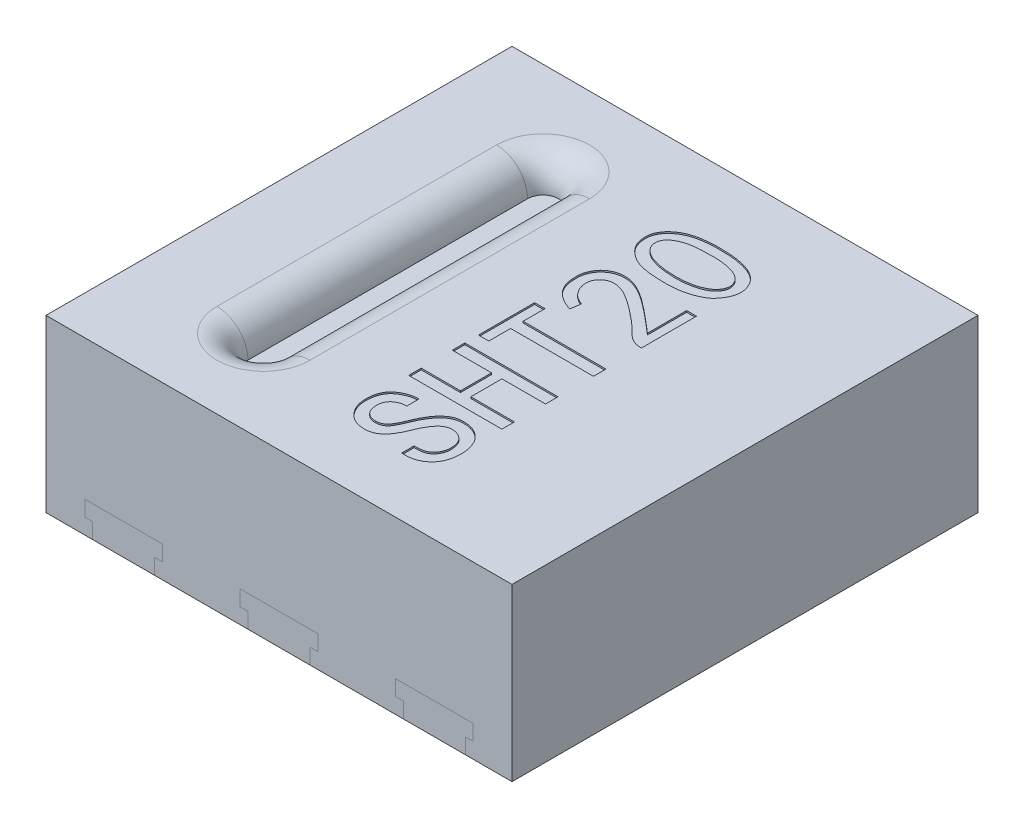
SolidWorks part; units mm, degrees
ref_plane "前视基准面" through (0, 0, 0) normal (0, 0, 1) x (1, 0, 0)
ref_plane "上视基准面" through (0, 0, 0) normal (0, 1, 0) x (1, 0, 0)
ref_plane "右视基准面" through (0, 0, 0) normal (1, 0, 0) x (0, 0, -1)
sketch "草图1" plane through (0, 0, 0) normal (0, 1, 0) x (1, 0, 0)
  line L1 (0, 0) -> (3, 0)
  line L2 (0, 0) -> (0, 3)
  line L3 (0, 3) -> (3, 3)
  line L4 (3, 0) -> (3, 3)
  dimension "D1" = 3
  dimension "D2" = 3
extrude "凸台-拉伸1" add sketch "草图1" along normal blind 1.1
sketch "草图2" plane through (0, 0, 0) normal (0, -1, 0) x (1, 0, 0)
  line L0 (-0.1538, -1.5) -> (3.2278, -1.5) construction
  line L1 (1.5, 0.1616) -> (1.5, -3.1506) construction
  line L2 (0, 0) -> (3, 0) construction
  line L3 (3, -3) -> (0, -3) construction
  line L4 (0, -3) -> (0, 0) construction
  line L5 (3, 0) -> (3, -3) construction
  line L6 (2.6, -2.25) -> (2.7, -2.15)
  line L7 (0.3, 0) -> (0.3, -0.35)
  line L8 (0.3, -0.35) -> (0.35, -0.4)
  line L9 (0.35, -0.4) -> (0.65, -0.4)
  line L10 (0.65, -0.4) -> (0.7, -0.35)
  line L11 (0.4, -0.75) -> (2.6, -0.75)
  line L12 (0.3, -0.85) -> (0.3, -2.15)
  line L13 (0.4, -2.25) -> (2.6, -2.25)
  line L14 (2.7, -0.85) -> (2.7, -2.15)
  line L15 (0.7, -0.35) -> (0.7, 0)
  line L16 (0.3, 0) -> (0.7, 0)
  line L17 (0.4, 0.0671) -> (0.4, -0.4631) construction
  line L18 (1.4, 0.0671) -> (1.4, -0.4631) construction
  line L19 (1.3, 0) -> (1.7, 0)
  line L20 (1.3, 0) -> (1.3, -0.35)
  line L21 (1.7, -0.35) -> (1.7, 0)
  line L22 (1.65, -0.4) -> (1.7, -0.35)
  line L23 (1.35, -0.4) -> (1.65, -0.4)
  line L24 (1.3, -0.35) -> (1.35, -0.4)
  line L25 (2.4, 0.0671) -> (2.4, -0.4631) construction
  line L26 (2.3, 0) -> (2.7, 0)
  line L27 (2.3, 0) -> (2.3, -0.35)
  line L28 (2.7, -0.35) -> (2.7, 0)
  line L29 (2.65, -0.4) -> (2.7, -0.35)
  line L30 (2.35, -0.4) -> (2.65, -0.4)
  line L31 (2.3, -0.35) -> (2.35, -0.4)
  line L32 (2.3, -2.65) -> (2.35, -2.6)
  line L33 (2.35, -2.6) -> (2.65, -2.6)
  line L34 (2.65, -2.6) -> (2.7, -2.65)
  line L35 (1.3, -2.65) -> (1.35, -2.6)
  line L36 (1.35, -2.6) -> (1.65, -2.6)
  line L37 (1.65, -2.6) -> (1.7, -2.65)
  line L38 (0.65, -2.6) -> (0.7, -2.65)
  line L39 (0.35, -2.6) -> (0.65, -2.6)
  line L40 (0.3, -2.65) -> (0.35, -2.6)
  line L41 (0.4, -3.0671) -> (0.4, -2.5369) construction
  line L42 (0.7, -2.65) -> (0.7, -3)
  line L43 (0.3, -3) -> (0.3, -2.65)
  line L44 (2.4, -3.0671) -> (2.4, -2.5369) construction
  line L45 (2.7, -2.65) -> (2.7, -3)
  line L46 (2.3, -3) -> (2.3, -2.65)
  line L47 (1.4, -3.0671) -> (1.4, -2.5369) construction
  line L48 (1.7, -2.65) -> (1.7, -3)
  line L49 (1.3, -3) -> (1.3, -2.65)
  line L50 (0.3, -3) -> (0.7, -3)
  line L51 (1.3, -3) -> (1.7, -3)
  line L52 (2.3, -3) -> (2.7, -3)
  arc A0 (0.3, -2.15) -> (0.4, -2.25) centre (0.4, -2.15) ccw
  arc A2 (2.7, -0.85) -> (2.6, -0.75) centre (2.6, -0.85) ccw
  arc A3 (0.3, -0.85) -> (0.4, -0.75) centre (0.4, -0.85) cw
  dimension "D5" = 0.2
  dimension "D1" = 2.4
  dimension "D2" = 1.5
  dimension "D3" = 0.1
  dimension "D4" = 0.1
  dimension "D6" = 0.3
  dimension "D7" = 0.4
  dimension "D8" = 0.4
  dimension "D9" = 135
  dimension "D10" = 135
  dimension "D11" = 0.05
  dimension "D13" = 2
  dimension "D12" = 3
sketch "草图3" plane through (0, 0, 0) normal (0, 0, 1) x (1, 0, 0)
  line L0 (0.3, 0) -> (0.3, 0.1)
  line L1 (0.3, 0) -> (0.7, 0) construction
  line L2 (-0.1538, 0) -> (3.2278, 0) construction
  line L3 (0.3, 0.1) -> (0.25, 0.1)
  line L4 (0.25, 0.1) -> (0.25, 0.2)
  line L5 (0.25, 0.2) -> (0.75, 0.2)
  line L6 (0.75, 0.2) -> (0.75, 0.1)
  line L7 (0.75, 0.1) -> (0.7, 0.1)
  line L8 (0.7, 0.1) -> (0.7, 0)
  line L9 (0, 0) -> (3, 0) construction
  line L10 (0, 1.1) -> (0, 0) construction
  line L11 (0.3, 0) -> (0.7, 0)
  line L12 (1.3, 0) -> (1.3, 0.1)
  line L13 (1.3, 0.1) -> (1.25, 0.1)
  line L14 (1.25, 0.1) -> (1.25, 0.2)
  line L15 (1.25, 0.2) -> (1.75, 0.2)
  line L16 (1.75, 0.2) -> (1.75, 0.1)
  line L17 (1.75, 0.1) -> (1.7, 0.1)
  line L18 (1.7, 0.1) -> (1.7, 0)
  line L19 (1.3, 0) -> (1.7, 0)
  line L20 (2.3, 0) -> (2.3, 0.1)
  line L21 (2.3, 0.1) -> (2.25, 0.1)
  line L22 (2.25, 0.1) -> (2.25, 0.2)
  line L23 (2.25, 0.2) -> (2.75, 0.2)
  line L24 (2.75, 0.2) -> (2.75, 0.1)
  line L25 (2.75, 0.1) -> (2.7, 0.1)
  line L26 (2.7, 0.1) -> (2.7, 0)
  line L27 (2.3, 0) -> (2.7, 0)
  line L28 (0.5, 0.3136) -> (0.5, -0.1006) construction
  line L29 (1.5, 0.2859) -> (1.5, -0.1006) construction
  dimension "D1" = 0.2
  dimension "D2" = 0.1
  dimension "D3" = 0.4
  dimension "D4" = 0.5
  dimension "D5" = 0.3
  dimension "D7" = 1
  dimension "D6" = 3
split line "分割线1"
split line "分割线2"
sketch "草图4" plane through (0, 0, -3) normal (0, 0, -1) x (-1, 0, 0)
  line L8 (-2.7, 0) -> (-2.7, 0.1)
  line L9 (-2.7, 0.1) -> (-2.75, 0.1)
  line L10 (-2.75, 0.1) -> (-2.75, 0.2)
  line L11 (-2.75, 0.2) -> (-2.25, 0.2)
  line L12 (-2.25, 0.2) -> (-2.25, 0.1)
  line L13 (-2.25, 0.1) -> (-2.3, 0.1)
  line L14 (-2.3, 0.1) -> (-2.3, 0)
  line L15 (-2.3, 0) -> (-2.7, 0)
  line L24 (-2.75, 0.2) -> (-2.25, 0.2) construction
  line L25 (-2.25, 0.2) -> (-2.25, 0.1) construction
  line L26 (-2.25, 0.1) -> (-2.3, 0.1) construction
  line L27 (-2.3, 0.1) -> (-2.3, 0) construction
  line L28 (-2.3, 0) -> (-2.7, 0) construction
  line L29 (-2.7, 0) -> (-2.7, 0.1) construction
  line L30 (-2.7, 0.1) -> (-2.75, 0.1) construction
  line L31 (-2.75, 0.1) -> (-2.75, 0.2) construction
  line L32 (-1.7, 0) -> (-1.7, 0.1)
  line L33 (-1.7, 0.1) -> (-1.75, 0.1)
  line L34 (-1.75, 0.1) -> (-1.75, 0.2)
  line L35 (-1.75, 0.2) -> (-1.25, 0.2)
  line L36 (-1.25, 0.2) -> (-1.25, 0.1)
  line L37 (-1.25, 0.1) -> (-1.3, 0.1)
  line L38 (-1.3, 0.1) -> (-1.3, 0)
  line L39 (-1.3, 0) -> (-1.7, 0)
  line L40 (-2.75, 0.2) -> (-2.25, 0.2) construction
  line L41 (-2.25, 0.2) -> (-2.25, 0.1) construction
  line L42 (-2.25, 0.1) -> (-2.3, 0.1) construction
  line L43 (-2.3, 0.1) -> (-2.3, 0) construction
  line L44 (-2.3, 0) -> (-2.7, 0) construction
  line L45 (-2.7, 0) -> (-2.7, 0.1) construction
  line L46 (-2.7, 0.1) -> (-2.75, 0.1) construction
  line L47 (-2.75, 0.1) -> (-2.75, 0.2) construction
  line L48 (-2.7, 0) -> (-2.3, 0) construction
  line L49 (-1.75, 0.2) -> (-1.25, 0.2) construction
  line L50 (-1.25, 0.2) -> (-1.25, 0.1) construction
  line L51 (-1.25, 0.1) -> (-1.3, 0.1) construction
  line L52 (-1.3, 0.1) -> (-1.3, 0) construction
  line L53 (-1.3, 0) -> (-1.7, 0) construction
  line L54 (-1.7, 0) -> (-1.7, 0.1) construction
  line L55 (-1.7, 0.1) -> (-1.75, 0.1) construction
  line L56 (-1.75, 0.1) -> (-1.75, 0.2) construction
  line L57 (-1.7, 0) -> (-1.3, 0) construction
  line L58 (-0.7, 0) -> (-0.7, 0.1)
  line L59 (-0.7, 0.1) -> (-0.75, 0.1)
  line L60 (-0.75, 0.1) -> (-0.75, 0.2)
  line L61 (-0.75, 0.2) -> (-0.25, 0.2)
  line L62 (-0.25, 0.2) -> (-0.25, 0.1)
  line L63 (-0.25, 0.1) -> (-0.3, 0.1)
  line L64 (-0.3, 0.1) -> (-0.3, 0)
  line L65 (-0.3, 0) -> (-0.7, 0)
  line L66 (-0.75, 0.2) -> (-0.25, 0.2) construction
  line L67 (-0.25, 0.2) -> (-0.25, 0.1) construction
  line L68 (-0.25, 0.1) -> (-0.3, 0.1) construction
  line L69 (-0.3, 0.1) -> (-0.3, 0) construction
  line L70 (-0.3, 0) -> (-0.7, 0) construction
  line L71 (-0.7, 0) -> (-0.7, 0.1) construction
  line L72 (-0.7, 0.1) -> (-0.75, 0.1) construction
  line L73 (-0.75, 0.1) -> (-0.75, 0.2) construction
  line L74 (-0.7, 0) -> (-0.3, 0) construction
  dimension "D1" = 3
  dimension "D2" = 1
split line "分割线7"
sketch "草图6" plane through (0, 1.1, 0) normal (0, 1, 0) x (1, 0, 0)
  line L0 (0.8, -0.4869) -> (0.8, 3.3115) construction
  line L1 (-0.3983, 1.5) -> (3.0727, 1.5) construction
  line L2 (3, 3) -> (0, 3) construction
  line L3 (0, 0) -> (3, 0) construction
  line L4 (3, 0) -> (3, 3) construction
  line L7 (0.7, 0.6) -> (0.7, 2.4)
  line L9 (0.9, 0.6) -> (0.9, 2.4)
  arc A0 (0.9, 2.4) -> (0.7, 2.4) centre (0.8, 2.4) ccw
  arc A1 (0.7, 0.6) -> (0.9, 0.6) centre (0.8, 0.6) ccw
  dimension "D1" = 2.2
  dimension "D2" = 0.2
  dimension "D3" = 1.8
extrude "切除-拉伸1" cut sketch "草图6" against normal blind 0.2
fillet "圆角1" radius 0.2 4 edges at (0.8, 1.1, -2.5) (0.9, 1.1, -1.5) (0.8, 1.1, -0.5) (0.7, 1.1, -1.5)
sketch "草图9" plane through (0, 1.1, 0) normal (0, 1, 0) x (1, 0, 0)
  line L0 (2.1196, 0.3452) -> (2.1196, 3.1693) construction
  text T0 "SHT20" font "黑体" height 0.6
extrude "切除-拉伸2" cut sketch "草图9" against normal blind 0.01
